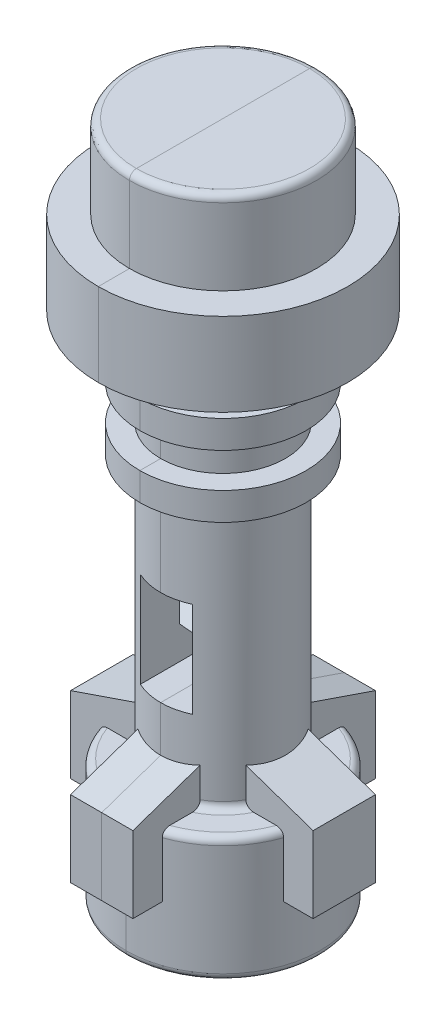
SolidWorks part; units mm, degrees
material "6061-T6 (SS)"
ref_plane "Front Plane" through (0, 0, 0) normal (0, 0, 1) x (1, 0, 0)
ref_plane "Top Plane" through (0, 0, 0) normal (0, 1, 0) x (1, 0, 0)
ref_plane "Right Plane" through (0, 0, 0) normal (1, 0, 0) x (0, 0, -1)
sketch "Sketch1" plane through (0, 0, 0) normal (0, 1, 0) x (1, 0, 0)
  circle A0 centre (0, 0) radius 4.5
extrude "Boss-Extrude1" add sketch "Sketch1" along normal blind 19
sketch "Sketch2" plane through (0, 0, 0) normal (0, -1, 0) x (1, 0, 0)
  circle A0 centre (0, 0) radius 7
  dimension "D1" = 14
extrude "Boss-Extrude2" add sketch "Sketch2" along normal blind 9
sketch "Sketch3" plane through (0, 19, 0) normal (0, 1, 0) x (1, 0, 0)
  circle A0 centre (0, 0) radius 6
extrude "Boss-Extrude3" add sketch "Sketch3" along normal blind 2
sketch "Sketch4" plane through (0, 21, 0) normal (0, 1, 0) x (1, 0, 0)
  circle A0 centre (0, 0) radius 4.5
extrude "Boss-Extrude4" add sketch "Sketch4" along normal blind 2.5
sketch "Sketch5" plane through (0, 23.5, 0) normal (0, 1, 0) x (1, 0, 0)
  circle A0 centre (0, 0) radius 6
extrude "Boss-Extrude5" add sketch "Sketch5" along normal blind 2
sketch "Sketch6" plane through (0, 25.5, 0) normal (0, 1, 0) x (1, 0, 0)
  circle A0 centre (0, 0) radius 4.5
extrude "Boss-Extrude6" add sketch "Sketch6" along normal blind 2.5
sketch "Sketch7" plane through (0, 28, 0) normal (0, 1, 0) x (1, 0, 0)
  circle A0 centre (0, 0) radius 9
  dimension "D1" = 18
extrude "Boss-Extrude7" add sketch "Sketch7" along normal blind 6
sketch "Sketch8" plane through (0, 34, 0) normal (0, 1, 0) x (1, 0, 0)
  circle A0 centre (0, 0) radius 6.75
extrude "Boss-Extrude8" add sketch "Sketch8" along normal blind 6
sketch "Sketch10" plane through (0, 0, 0) normal (1, 0, 0) x (0, 0, -1)
  line L1 (-8.75, -4.5) -> (8.75, -4.5)
  line L6 (8.75, -4.5) -> (8.75, 1)
  line L7 (0, 4) -> (-8.75, 1)
  line L9 (0, 9.9) -> (0, -9.9) construction
  line L10 (-8.75, -4.5) -> (-8.75, 1)
  line L12 (0, 4) -> (8.75, 1)
  point P6 (0, -4.5)
extrude "Boss-Extrude9" add sketch "Sketch10" along normal blind 2.25 and the other way blind 2.25
pattern_circular "CirPattern1" count 2 every 90 about axis through (0, 19, 0) along (0, -1, 0) of "Boss-Extrude9"
sketch "Sketch11" plane through (0, 40, 0) normal (0, 1, 0) x (1, 0, 0)
  circle A0 centre (0, 0) radius 5.25
  dimension "D1" = 10.5
sketch "Sketch12" plane through (0, -9, 0) normal (0, -1, 0) x (1, 0, 0)
  circle A0 centre (0, 0) radius 5.25
  dimension "D1" = 10.5
fillet "Fillet1" radius 0.5 9 edges at (4.9497, 0, -4.9497) (-4.9497, 0, -4.9497) (-4.9497, 0, 4.9497) (0, -9, -7) (4.9497, 0, 4.9497) (-3.182, 0, -3.182) (3.182, 0, -3.182) (3.182, 0, 3.182) (-3.182, 0, 3.182)
fillet "Fillet3" radius 0.5 1 edges at (0, 40, 6.75)
scale "Scale3" scale about origin uniform scaling yes scale factor 3.2
sketch "Sketch14" plane through (0, 0, 0) normal (0, 0, 1) x (1, 0, 0)
  line L0 (0, 60.8) -> (0, 1.6) construction
  line L1 (-6, 18.4) -> (6, 18.4)
  line L2 (-6, 18.4) -> (-6, 40.4)
  line L3 (-6, 40.4) -> (6, 40.4)
  line L4 (6, 18.4) -> (6, 40.4)
  line L5 (-6, 18.4) -> (6, 40.4) construction
  line L6 (-6, 40.4) -> (6, 18.4) construction
  line L8 (21.2113, -1.6) -> (7.2, -1.6) construction
  point P0 (0, 29.4)
  dimension "D1" = 22
  dimension "D2" = 12
  dimension "D3" = 20
extrude "Cut-Extrude1" cut sketch "Sketch14" against normal through all both and the other way through all
sketch "Sketch17" plane through (0, 0, 0) normal (1, 0, 0) x (0, 0, -1)
  line L0 (0, 40.4043) -> (-4.0535, 35.9806)
  line L1 (0, 60.8) -> (0, 1.6) construction
  line L2 (-4.0535, 35.9806) -> (-4.0535, 25.9806)
  line L3 (-4.0535, 25.9806) -> (0, 21.5569)
  line L4 (0, 21.5569) -> (4.0535, 25.9806)
  line L5 (4.0535, 25.9806) -> (4.0535, 35.9806)
  line L6 (4.0535, 35.9806) -> (0, 40.4043)
  dimension "D1" = 10
  dimension "D2" = 10
  dimension "D3" = 85
  dimension "D4" = 6
  dimension "D5" = 6
  dimension "D6" = 85
extrude "Cut-Extrude3" cut sketch "Sketch17" against normal through all
split "Split1" trim tools "Right Plane" bodies to split 118 resulting bodies 119 120
